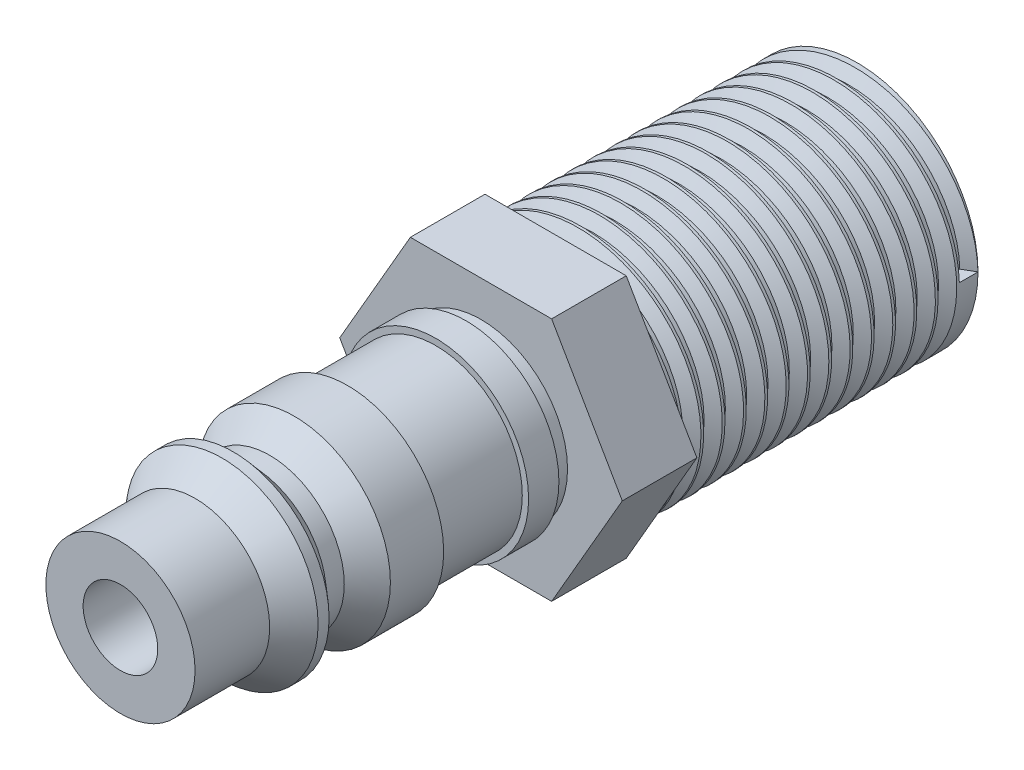
SolidWorks part; units mm, degrees
material "AISI 304"
ref_plane "Front Plane" through (0, 0, 0) normal (0, 0, 1) x (1, 0, 0)
ref_plane "Top Plane" through (0, 0, 0) normal (0, 1, 0) x (1, 0, 0)
ref_plane "Right Plane" through (0, 0, 0) normal (1, 0, 0) x (0, 0, -1)
sketch "Sketch1" plane through (0, 0, 0) normal (1, 0, 0) x (0, 0, -1)
  line L0 (0, 0) -> (0, 5.1435)
  line L1 (0, 5.1435) -> (-12.8335, 5.1435)
  line L2 (-12.8335, 5.1435) -> (-12.8335, 3.6833)
  line L3 (-12.8335, 3.6833) -> (-16.6435, 3.6833)
  line L4 (-16.6435, 3.6833) -> (-16.6435, 3.9516)
  line L5 (-16.6435, 3.9516) -> (-17.934, 3.9516)
  line L6 (-17.934, 3.9516) -> (-17.934, 3.6833)
  line L7 (-17.934, 3.6833) -> (-21.6882, 3.6833)
  line L8 (-21.6882, 3.6833) -> (-21.6882, 4.0905)
  line L9 (-21.6882, 4.0905) -> (-23.9546, 4.0905)
  line L10 (-23.9546, 4.0905) -> (-25.0031, 3.175)
  line L11 (-25.0031, 3.175) -> (-25.7651, 3.175)
  line L12 (-25.7651, 3.175) -> (-26.5613, 4.087)
  line L13 (-26.5613, 4.087) -> (-27.0283, 4.087)
  line L14 (-27.0283, 4.087) -> (-28.1781, 3.175)
  line L15 (-28.1781, 3.175) -> (-31.3531, 3.175)
  line L16 (-31.3531, 3.175) -> (-31.3531, 0)
  line L17 (-31.3531, 0) -> (0, 0)
  line L18 (0, 0) -> (2.9494, 0) construction
  dimension "D1" = 10.287
  dimension "D2" = 6.35
  dimension "D3" = 3.175
  dimension "D4" = 3.81
  dimension "D5" = 6.35
  dimension "D6" = 5.588
  dimension "D7" = 31.3531
revolve "Revolve1" add sketch "Sketch1" angle 360 about L18
sketch "Sketch3" plane through (0, 0, 12.8335) normal (0, 0, 1) x (1, 0, 0)
  line L1 (3.0063, 5.207) -> (-3.0063, 5.207)
  line L2 (-3.0063, 5.207) -> (-6.0125, 0)
  line L3 (-6.0125, 0) -> (-3.0063, -5.207)
  line L4 (-3.0063, -5.207) -> (3.0063, -5.207)
  line L5 (3.0063, -5.207) -> (6.0125, 0)
  line L6 (6.0125, 0) -> (3.0063, 5.207)
  circle A0 centre (0, 0) radius 5.207 construction
  circle A1 centre (0, 0) radius 5.1435 construction
  dimension "D1" = 5.207
extrude "Boss-Extrude1" add sketch "Sketch3" along normal blind 3.175 contours L1 L2 L3 L4 L5 L6
sketch "Sketch2" plane through (0, 0, 31.3531) normal (0, 0, 1) x (1, 0, 0)
  circle A0 centre (0, 0) radius 1.5875
  dimension "D1" = 3.175
extrude "Cut-Extrude1" cut sketch "Sketch2" against normal up to surface (31.3531 mm away) up to face at (5.1435, 0, 0)
thread "Thread1" pitch 0.9071 method cut profile "Thread Profile1" start angle 0, offset 0, length 12.7, pitch 0.9071, diameter 10.287
ref_plane "Plane1" through (5.1435, 0, 0) normal (0, -1, 0) x (1, 0, 0)
sketch "Thread Profile1" plane through (5.1435, 0, 0) normal (0, -1, 0) x (1, 0, 0)
  line L0 (0, 0) -> (0, 0.9071) construction
  line L11 (0, 0) -> (0, 0.7937)
  line L12 (0, 0.7937) -> (-0.491, 0.5103)
  line L13 (-0.491, 0.5103) -> (-0.491, 0.2835)
  line L15 (-0.491, 0.2835) -> (0, 0)
  line L17 (-0.491, 0.3969) -> (0, 0.3969) construction
  point P2 (0, 0)
  dimension "Pitch" = 0.9071
  dimension "Profile_Angle" = 60
  dimension "Profile_Land" = 0.2268
  dimension "Profile_Height" = 0.491
